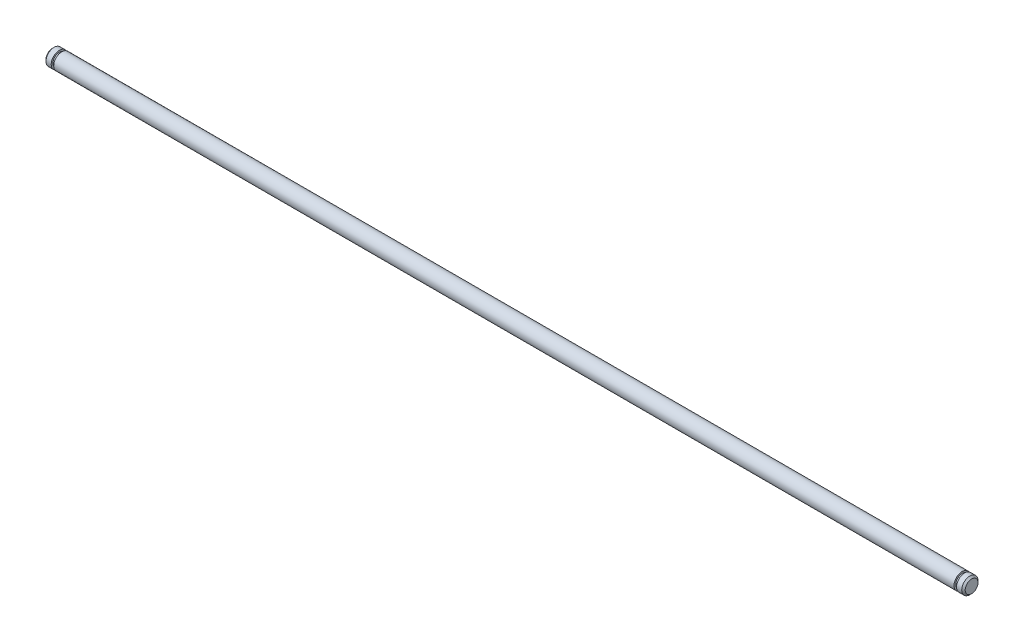
SolidWorks part; units mm, degrees
material "Alloy Steel"
ref_plane "Front" through (0, 0, 0) normal (0, 0, 1) x (1, 0, 0)
ref_plane "Top" through (0, 0, 0) normal (0, 1, 0) x (1, 0, 0)
ref_plane "Right" through (0, 0, 0) normal (1, 0, 0) x (0, 0, -1)
ref_axis "side-side" through (80.9, 0, 0) along (-1, 0, 0)
ref_axis "up-down" through (0, 50, 0) along (0, -1, 0)
ref_axis "front-back" through (0, 0, -80.9) along (0, 0, 1)
sketch "Sketch1" plane through (0, 0, 0) normal (0, 0, 1) x (1, 0, 0)
  line L0 (-29.7868, 0) -> (33.5279, 0) construction
  line L1 (0, -50) -> (0, 50) construction
  line L2 (-152.7556, 0) -> (116.3066, 0)
  line L3 (-152.7556, 0) -> (-152.7556, 2.3813)
  line L4 (-152.7556, 2.3813) -> (-150.7236, 2.3813)
  line L5 (116.3066, 0) -> (116.3066, 2.3813)
  line L6 (116.3066, 0) -> (187.0165, 0) construction
  line L7 (114.2746, 2.3813) -> (114.2746, 1.8669)
  line L8 (114.2746, 1.8669) -> (113.538, 1.8669)
  line L9 (113.538, 2.3813) -> (113.538, 1.8669)
  line L10 (-149.987, 2.3812) -> (113.538, 2.3813)
  line L11 (114.2746, 2.3813) -> (116.3066, 2.3813)
  line L12 (-150.7236, 2.3813) -> (-150.7236, 1.8669)
  line L13 (-150.7236, 1.8669) -> (-149.987, 1.8669)
  line L14 (-149.987, 2.3812) -> (-149.987, 1.8669)
  point P13 (113.538, 2.1241)
  dimension "D1" = 0.7366
  dimension "D2" = 2.032
  dimension "D3" = 4.7625
  dimension "D4" = 3.7338
  dimension "D5" = 113.538
  dimension "D6" = 149.987
revolve "Revolve1" add sketch "Sketch1" angle 360 about L6
chamfer "Chamfer1" distance 0.508 angle 45 2 edges at (-152.7556, 0, 2.3813) (116.3066, 0, 2.3813)
